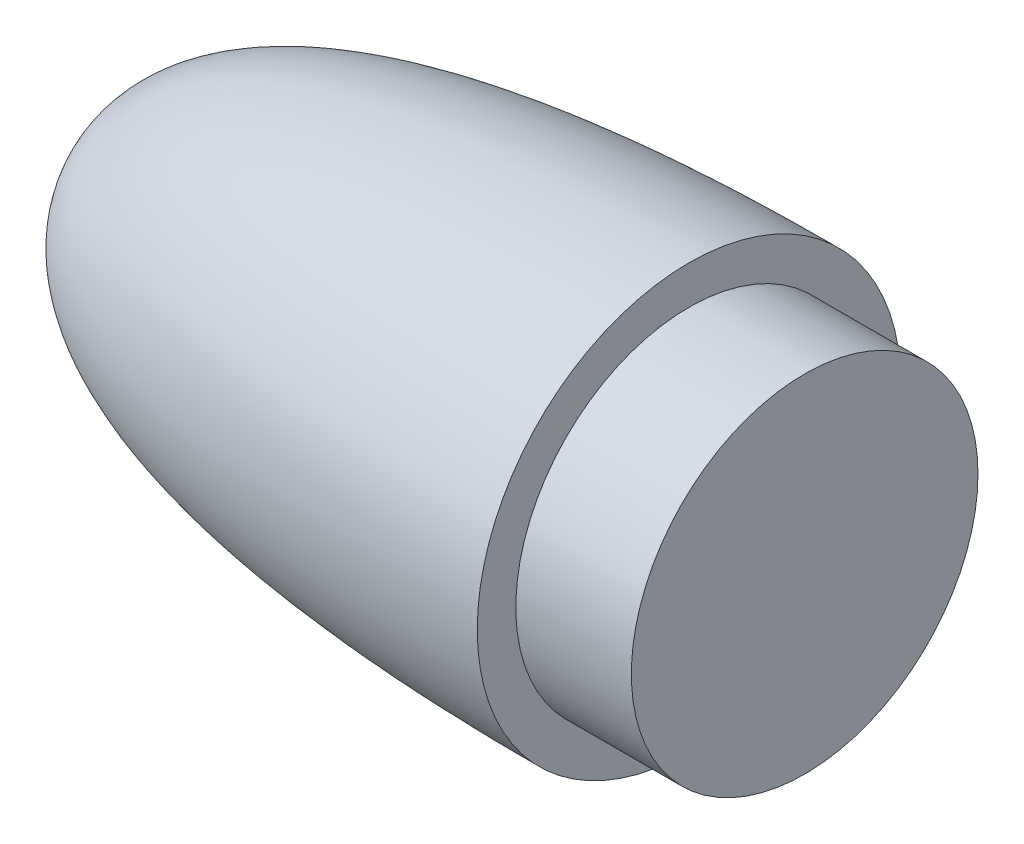
SolidWorks part; units mm, degrees
ref_plane "Front Plane" through (0, 0, 0) normal (0, 0, 1) x (1, 0, 0)
ref_plane "Top Plane" through (0, 0, 0) normal (0, 1, 0) x (1, 0, 0)
ref_plane "Right Plane" through (0, 0, 0) normal (1, 0, 0) x (0, 0, -1)
sketch "Sketch1" plane through (0, 0, 0) normal (0, 1, 0) x (1, 0, 0)
  line L0 (-15, 0) -> (-15, -5)
  line L1 (0, 0) -> (-15, 0)
  line L2 (0, 0) -> (0, 45)
  line L3 (0, 45) -> (-15, 45)
  line L4 (-15, 0) -> (-15, 45)
  line L5 (-15, 45) -> (-15, 50)
  line L6 (-15, 22.5) -> (-91.2, 22.5)
  line L7 (-15, -5) -> (-91.2, -5) construction
  line L8 (-91.2, -5) -> (-91.2, 22.5) construction
  line L9 (-15, 50) -> (-91.2, 50) construction
  line L10 (-91.2, 50) -> (-91.2, 22.5) construction
  line L11 (-15, 22.5) -> (0, 22.5)
  spline S0 degree 2 poles (-15, -5) (-91.2, -5) (-91.2, 22.5) knots 0 0 0 1 1 1
  spline S1 degree 2 poles (-15, 50) (-91.2, 50) (-91.2, 22.5) knots 0 0 0 1 1 1
  dimension "D1" = 45
  dimension "D2" = 15
  dimension "D3" = 5
  dimension "D4" = 5
  dimension "D5" = 76.2
revolve "Revolve2" add sketch "Sketch1" angle 360 about L6 region at (-48.528, 0, -34.6) region at (-7.5, 0, -33.75)
